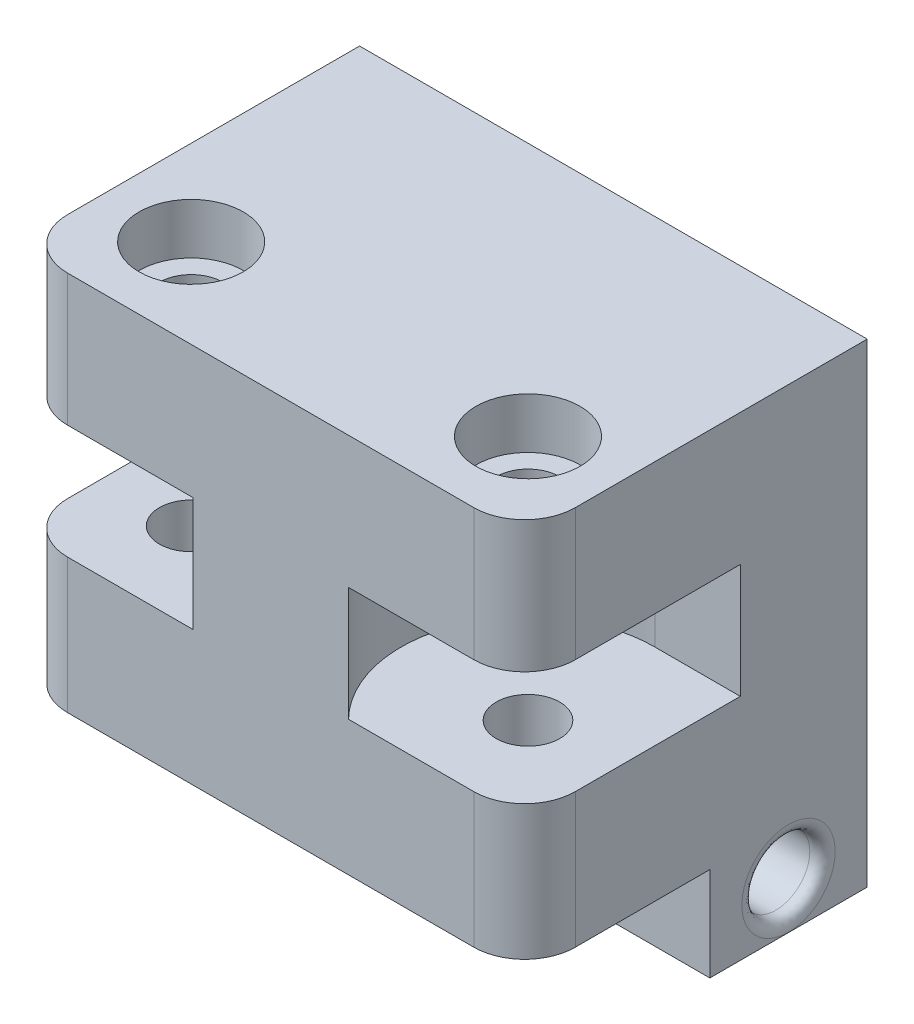
SolidWorks part; units mm, degrees
ref_plane "Front Plane" through (0, 0, 0) normal (0, 0, 1) x (1, 0, 0)
ref_plane "Top Plane" through (0, 0, 0) normal (0, 1, 0) x (1, 0, 0)
ref_plane "Right Plane" through (0, 0, 0) normal (1, 0, 0) x (0, 0, -1)
sketch "Sketch1" plane through (0, 0, 0) normal (0, 1, 0) x (1, 0, 0)
  line L1 (-22.8462, -9.1868) -> (17.1538, -9.1868)
  line L2 (-22.8462, -9.1868) -> (-22.8462, 17.8132)
  line L3 (-22.8462, 17.8132) -> (17.1538, 17.8132)
  line L4 (17.1538, -9.1868) -> (17.1538, 17.8132)
  dimension "D1" = 27
  dimension "D2" = 40
extrude "Boss-Extrude1" add sketch "Sketch1" along normal blind 30
sketch "Sketch2" plane through (0, 0, -17.8132) normal (0, 0, -1) x (-1, 0, 0)
  line L0 (2.8462, 30) -> (2.8462, 0) construction
  line L1 (-8.0864, 4) -> (-0.2064, 4)
  line L2 (-0.2064, 4) -> (-0.2064, 7)
  line L3 (-0.2064, 7) -> (-2.8664, 7)
  line L4 (-2.8664, 7) -> (-2.8664, 8.0087)
  line L5 (-2.8664, 8.0087) -> (-0.2538, 10.6287)
  line L6 (-0.2538, 10.6287) -> (5.9462, 10.6287)
  line L7 (-17.1538, 30) -> (22.8462, 30) construction
  line L8 (-17.1538, 0) -> (22.8462, 0) construction
  line L9 (-8.0864, 4) -> (-8.0864, 26)
  line L10 (-8.0864, 26) -> (-0.2064, 26)
  line L11 (-0.2064, 26) -> (-0.2064, 23)
  line L12 (-0.2064, 23) -> (-2.8664, 23)
  line L13 (-2.8664, 23) -> (-2.8664, 21.9913)
  line L14 (-2.8664, 21.9913) -> (-0.2464, 19.3787)
  line L15 (-0.2464, 19.3787) -> (5.9536, 19.3787)
  line L16 (-17.1538, 15) -> (22.8462, 15) construction
  line L17 (-17.1538, 30) -> (-17.1538, 0) construction
  line L18 (22.8462, 30) -> (22.8462, 0) construction
  line L19 (5.9387, 19.3787) -> (-0.2613, 19.3787)
  line L20 (8.5587, 21.9913) -> (5.9387, 19.3787)
  line L21 (8.5587, 23) -> (8.5587, 21.9913)
  line L22 (5.8987, 23) -> (8.5587, 23)
  line L23 (5.8987, 26) -> (5.8987, 23)
  line L24 (13.7787, 26) -> (5.8987, 26)
  line L25 (13.7787, 4) -> (13.7787, 26)
  line L26 (8.5587, 8.0087) -> (5.9462, 10.6287)
  line L27 (8.5587, 7) -> (8.5587, 8.0087)
  line L28 (5.8987, 7) -> (8.5587, 7)
  line L29 (5.8987, 4) -> (5.8987, 7)
  line L30 (13.7787, 4) -> (5.8987, 4)
  point P26 (-8.0864, 15)
  point P27 (2.8462, 15)
  point P37 (2.8462, 10.6287)
  dimension "D1" = 6.2
  dimension "D2" = 2.62
  dimension "D3" = 3.7
  dimension "D4" = 8.75
  dimension "D5" = 7.88
  dimension "D6" = 22
  dimension "D7" = 5.22
  dimension "D8" = 3
  dimension "D9" = 90
extrude "Cut-Extrude1" cut sketch "Sketch2" against normal blind 10
sketch "Sketch3" plane through (0, 0, 0) normal (0, -1, 0) x (1, 0, 0)
  line L0 (-22.8462, 9.1868) -> (17.1538, 9.1868) construction
  line L1 (17.1538, 9.1868) -> (17.1538, -17.8132) construction
  line L2 (-2.8462, 9.1868) -> (-2.8462, -17.8132) construction
  line L3 (17.1538, -17.8132) -> (-22.8462, -17.8132) construction
  circle A0 centre (10.4238, 2.1868) radius 2.5
  circle A2 centre (-16.1162, 2.1868) radius 2.5
  dimension "D1" = 5
  dimension "D3" = 7
  dimension "D4" = 6.73
extrude "Cut-Extrude2" cut sketch "Sketch3" against normal blind 30
sketch "Sketch8" plane through (0, 0, 0) normal (0, -1, 0) x (1, 0, 0)
  line L0 (3.2824, 9.1868) -> (17.1538, 9.1868)
  line L1 (-22.8462, 9.1868) -> (17.1538, 9.1868) construction
  line L2 (17.1538, 9.1868) -> (17.1538, -7.8132)
  line L3 (17.1538, 9.1868) -> (17.1538, -17.8132) construction
  line L4 (17.1538, -7.8132) -> (10.4238, -7.8132)
  line L6 (-2.8462, -17.8132) -> (-2.8462, 9.1868) construction
  line L7 (17.1538, -17.8132) -> (-22.8462, -17.8132) construction
  line L8 (-22.8462, -7.8132) -> (-16.1162, -7.8132)
  line L9 (-22.8462, 9.1868) -> (-22.8462, -7.8132)
  line L10 (-8.9747, 9.1868) -> (-22.8462, 9.1868)
  arc A0 (10.4238, -7.8132) -> (3.2824, 9.1868) centre (10.4238, 2.1868) cw
  arc A1 (-16.1162, -7.8132) -> (-8.9747, 9.1868) centre (-16.1162, 2.1868) ccw
  dimension "D1" = 10
extrude "Cut-Extrude5" cut sketch "Sketch8" against normal blind 9 from offset 10.62 offset against normal yes
sketch "Sketch10" plane through (8.0864, 0, 0) normal (-1, 0, 0) x (0, 0, 1)
  line L0 (-17.8132, 30) -> (-17.8132, 0) construction
  line L1 (-17.8132, 19.62) -> (2.1868, 19.62)
  line L2 (-17.8132, 19.62) -> (-17.8132, 10.62)
  line L3 (-17.8132, 10.62) -> (2.1868, 10.62)
  line L4 (2.1868, 19.62) -> (2.1868, 10.62)
  line L6 (9.1868, 19.62) -> (-7.8132, 19.62) construction
  line L7 (9.1868, 10.62) -> (-7.8132, 10.62) construction
  dimension "D1" = 20
extrude "Cut-Extrude7" cut sketch "Sketch10" along normal blind 6.8
sketch "Sketch12" plane through (-13.7787, 0, 0) normal (1, 0, 0) x (0, 0, -1)
  line L0 (-9.1868, 19.62) -> (1.8761, 19.62) construction
  line L1 (17.8132, 19.62) -> (-2.1868, 19.62)
  line L2 (17.8132, 19.62) -> (17.8132, 10.62)
  line L3 (17.8132, 10.62) -> (-2.1868, 10.62)
  line L4 (-2.1868, 19.62) -> (-2.1868, 10.62)
  line L6 (7.8132, 10.62) -> (-9.1868, 10.62) construction
  line L7 (17.8132, 30) -> (17.8132, 0) construction
  dimension "D1" = 20
extrude "Cut-Extrude10" cut sketch "Sketch12" along normal blind 6.8
fillet "Fillet1" radius 4 4 edges at (17.1538, 5.31, 9.1868) (17.1538, 24.81, 9.1868) (-22.8462, 5.31, 9.1868) (-22.8462, 24.81, 9.1868)
sketch "Sketch13" plane through (17.1538, 0, 0) normal (1, 0, 0) x (0, 0, -1)
  line L0 (-5.1868, 0) -> (17.8132, 0) construction
  line L1 (17.8132, 30) -> (17.8132, 0) construction
  line L3 (17.8132, 0) -> (5.4132, 0)
  line L4 (17.8132, 0) -> (17.8132, -7.4)
  line L5 (17.8132, -7.4) -> (5.4132, -7.4)
  line L6 (5.4132, 0) -> (5.4132, -7.4)
  circle A0 centre (11.6132, -3.7) radius 2.675
  dimension "D1" = 6.2
  dimension "D2" = 3.7
  dimension "D3" = 5.35
  dimension "D4" = 12.4
  dimension "D5" = 7.4
extrude "Boss-Extrude2" add sketch "Sketch13" against normal up to surface (40 mm away) up to face at (-22.8462, 15.06, -3.8132)
sketch "Sketch14" plane through (0, 0, -5.4132) normal (0, 0, 1) x (1, 0, 0)
  line L0 (-22.8462, -7.4) -> (17.1538, -7.4) construction
  line L1 (-12.8462, -7.4) -> (7.1538, -7.4)
  line L2 (-12.8462, -7.4) -> (-12.8462, 0)
  line L3 (-12.8462, 0) -> (7.1538, 0)
  line L4 (7.1538, -7.4) -> (7.1538, 0)
  line L5 (-18.8462, 0) -> (13.1538, 0) construction
  line L7 (17.1538, 0) -> (17.1538, -7.4) construction
  dimension "D1" = 20
  dimension "D2" = 10
extrude "Cut-Extrude11" cut sketch "Sketch14" against normal up to next
sketch "Sketch15" plane through (0, 30, 0) normal (0, 1, 0) x (1, 0, 0)
  line L0 (-2.8462, 17.8132) -> (-2.8462, -9.1868) construction
  line L13 (17.1538, 17.8132) -> (-22.8462, 17.8132) construction
  line L14 (-18.8462, -9.1868) -> (13.1538, -9.1868) construction
  circle A4 centre (-16.1162, -2.1868) radius 4.1
  circle A5 centre (10.4238, -2.1868) radius 4.1
  dimension "D1" = 8.2
extrude "Cut-Extrude12" cut sketch "Sketch15" against normal blind 4
sketch "Sketch16" plane through (0, 0, 0) normal (0, -1, 0) x (1, 0, 0)
  line L1 (-13.749, -1.9132) -> (-11.3819, 2.1868)
  line L2 (-11.3819, 2.1868) -> (-13.749, 6.2868)
  line L3 (-13.749, 6.2868) -> (-18.4833, 6.2868)
  line L4 (-18.4833, 6.2868) -> (-20.8504, 2.1868)
  line L5 (-20.8504, 2.1868) -> (-18.4833, -1.9132)
  line L6 (-18.4833, -1.9132) -> (-13.749, -1.9132)
  line L7 (12.791, -1.9132) -> (15.1581, 2.1868)
  line L8 (15.1581, 2.1868) -> (12.791, 6.2868)
  line L9 (12.791, 6.2868) -> (8.0567, 6.2868)
  line L10 (8.0567, 6.2868) -> (5.6896, 2.1868)
  line L11 (5.6896, 2.1868) -> (8.0567, -1.9132)
  line L12 (8.0567, -1.9132) -> (12.791, -1.9132)
  circle A0 centre (10.4238, 2.1868) radius 2.5 construction
  circle A1 centre (-16.1162, 2.1868) radius 2.5 construction
  circle A2 centre (10.4238, 2.1868) radius 2.5
  circle A3 centre (-16.1162, 2.1868) radius 2.5
  circle A4 centre (-16.1162, 2.1868) radius 4.1 construction
  circle A5 centre (10.4238, 2.1868) radius 4.1 construction
  dimension "D1" = 8.2
  dimension "D2" = 8.2
extrude "Cut-Extrude13" cut sketch "Sketch16" against normal blind 4
fillet "Fillet2" radius 1 2 edges at (-22.8462, -3.7, -14.2882) (17.1538, -3.7, -14.2882) conic rho 0.5
